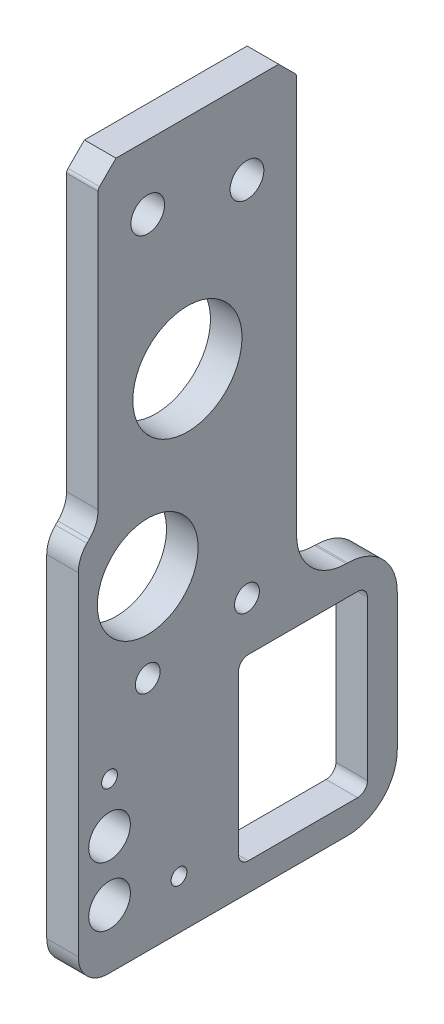
SolidWorks part; units mm, degrees
material "6061 Alloy"
ref_plane "Front Plane" through (0, 0, 0) normal (0, 0, 1) x (1, 0, 0)
ref_plane "Top Plane" through (0, 0, 0) normal (0, 1, 0) x (1, 0, 0)
ref_plane "Right Plane" through (0, 0, 0) normal (1, 0, 0) x (0, 0, -1)
sketch "Sketch1" plane through (0, 0, 0) normal (1, 0, 0) x (0, 0, -1)
  line L2 (0, 0) -> (0, 37.775)
  line L3 (0, 37.775) -> (2, 39.775)
  line L4 (2, 39.775) -> (2, 70.81)
  line L5 (2, 70.81) -> (22, 70.81)
  line L14 (-6.9356, -2) -> (62.4069, -2) construction
  line L15 (7, 37.775) -> (0, 37.775) construction
  line L23 (22, 70.81) -> (22, 23.81)
  line L31 (22, 23.81) -> (32.15, 23.81)
  line L32 (32.15, 23.81) -> (32.15, 0)
  line L33 (32.15, 0) -> (0, 0)
  line L35 (22.65, 20.81) -> (22.65, 2.81) construction
  line L36 (16.15, 20.81) -> (29.15, 20.81)
  line L37 (16.15, 20.81) -> (16.15, 2.81)
  line L38 (16.15, 2.81) -> (29.15, 2.81)
  line L39 (29.15, 20.81) -> (29.15, 2.81)
  circle A0 centre (7, 32.7) radius 5.075
  circle A1 centre (7, 64.31) radius 1.7
  circle A2 centre (17, 62.31) radius 1.7
  circle A5 centre (3.15, 5.95) radius 2.1
  circle A6 centre (3.15, 11.95) radius 2.1
  circle A9 centre (10.15, 4.95) radius 0.8
  circle A10 centre (3.15, 16.95) radius 0.8
  point P1 (7, 23.81)
  point P2 (17, 25.81)
  dimension "D11" = 10.15
  dimension "D13" = 3.4
  dimension "D17" = 15
  dimension "D21" = 2
  dimension "D33" = 4.2
  dimension "D36" = 1.6
  dimension "D4" = 18
  dimension "D5" = 13
  dimension "D22" = 15.75
  dimension "D6" = 16.15
  dimension "D7" = 5
  dimension "D8" = 2
  dimension "D9" = 2
  dimension "D10" = 47
  dimension "D12" = 34.7
  dimension "D14" = 8.5
  dimension "D15" = 6.5
  dimension "D16" = 5
  dimension "D18" = 38.11
  dimension "D19" = 3
  dimension "D20" = 3
  dimension "D23" = 7
  dimension "D24" = 20
  dimension "D25" = 5
  dimension "D28" = 2
  dimension "D30" = 6
  dimension "D32" = 3.15
  dimension "D38" = 12
extrude "Boss-Extrude1" add sketch "Sketch1" along normal blind 3.18
sketch "Sketch3" plane through (0, 0, 0) normal (-1, 0, 0) x (0, 0, 1)
  line L4 (-2, 70.81) -> (-2, 39.775) construction
  circle A0 centre (-11, 48.8109) radius 5.5
  circle A6 centre (-7, 32.7) radius 5.075 construction
  dimension "D1" = 11
  dimension "D3" = 16.6
  dimension "D2" = 9
extrude "Cut-Extrude4" cut sketch "Sketch3" against normal through all
sketch "Sketch8" [suppressed] plane through (3.18, 0, 0) normal (1, 0, 0) x (0, 0, -1)
  line L0 (2, 70.81) -> (2, 39.775) construction
  line L1 (11, 48.8109) -> (2, 48.8109) construction
  line L2 (2, 52.8109) -> (3.5, 52.8109)
  line L3 (3.5, 44.8109) -> (2, 44.8109)
  line L4 (2, 44.8109) -> (2, 52.8109)
  arc A0 (3.5, 44.8109) -> (3.5, 52.8109) centre (11, 48.8109) ccw
  circle A1 centre (7, 32.7) radius 5.075 construction
  point P11 (2, 48.8109)
  dimension "D1" = 16.6
  dimension "D2" = 17
  dimension "D3" = 9
  dimension "D4" = 8
extrude "Cut-Extrude5" [suppressed] cut sketch "Sketch8" against normal through all
fillet "Fillet2" radius 3 3 edges at (1.59, 37.775, 0) (1.59, 39.775, -2) (1.59, 0, 0)
fillet "Chamfer2" radius 1.8 2 edges at (1.59, 70.81, -22) (1.59, 70.81, -2) profile chamfer
fillet "Fillet4" radius 0.5 2 edges at (1.59, 69.01, -2) (1.59, 69.01, -22)
fillet "Fillet5" [suppressed] radius 0.3
sketch "BallRef" plane through (0, 0, 0) normal (-1, 0, 0) x (0, 0, 1)
  line L0 (-31.524, -10.56) -> (65.6624, -10.56) construction
  line L1 (-0.75, 32.7) -> (-0.75, 29.3885) construction
  line L2 (-0.75, 29.3885) -> (31.3703, 29.3885) construction
  line L3 (31.3703, 10.85) -> (31.3703, 29.3885) construction
  line L4 (1.092, -10.56) -> (-13.908, 4.44) construction
  line L5 (-13.908, 4.44) -> (-13.908, -10.56) construction
  line L6 (-13.908, -10.56) -> (1.092, -10.56) construction
  circle A0 centre (-7, 32.7) radius 6.25 construction
  circle A1 centre (9.9603, 10.85) radius 21.41 construction
  dimension "D1" = 12.5
  dimension "D2" = 42.82
  dimension "D3" = 43.26
  dimension "D4" = 45
  dimension "D5" = 15
hole_wizard "M2x0.4 Tapped Hole1" positions "3DSketch1" profile "Sketch12" tap size "M2x0.4" standard "ANSI Metric" end condition through all
sketch3d "3DSketch1"
  line L0 (3.18, 16.95, -3.15) -> (0, 16.95, -3.15) construction
  line L1 (3.18, 4.95, -10.15) -> (0, 4.95, -10.15) construction
  point P0 (0, 16.95, -3.15)
  point P4 (0, 4.95, -10.15)
sketch "Sketch12" plane through (0, 16.95, -3.15) normal (0, 1, 0) x (0, 0, 1)
  line L0 (0, 0) -> (0, 3.18)
  line L1 (0, 3.18) -> (0.8, 3.18)
  line L2 (0.8, 3.18) -> (0.8, 0)
  line L5 (0.8, 0) -> (0, 0)
  line L11 (0, -6.35) -> (0, 107.95) construction
  dimension "Thru Tap Drill Dia." = 1.6
  dimension "Thru Tap Drill Depth" = 3.18
cosmetic thread "Hole Thread3" parameters "D2"=2
cosmetic thread "Hole Thread4" parameters "D2"=2
fillet "Fillet9" radius 1 4 edges at (1.59, 2.81, -29.15) (1.59, 2.81, -16.15) (1.59, 20.81, -29.15) (1.59, 20.81, -16.15)
fillet "Fillet11" radius 5 3 edges at (1.59, 0, -32.15) (1.59, 23.81, -22) (1.59, 23.81, -32.15)
hole_wizard "M3x0.5 Tapped Hole1" positions "Sketch13" profile "Sketch14" tap size "M3x0.5" standard "ANSI Metric" end condition through all
sketch "Sketch13" plane through (3.18, 0, 0) normal (1, 0, 0) x (0, 0, -1)
  point P0 (7, 23.81)
  point P3 (17, 25.81)
sketch "Sketch14" plane through (3.18, 23.81, -7) normal (0, 1, 0) x (0, 0, -1)
  line L0 (0, 0) -> (0, 3.18)
  line L1 (0, 3.18) -> (1.25, 3.18)
  line L2 (1.25, 3.18) -> (1.25, 0)
  line L5 (1.25, 0) -> (0, 0)
  line L11 (0, -6.35) -> (0, 107.95) construction
  dimension "Thru Tap Drill Dia." = 2.5
  dimension "Thru Tap Drill Depth" = 3.18
cosmetic thread "Hole Thread5" parameters "D2"=3
cosmetic thread "Hole Thread6" parameters "D2"=3
equation "\"7.5.00mm\"=5"
